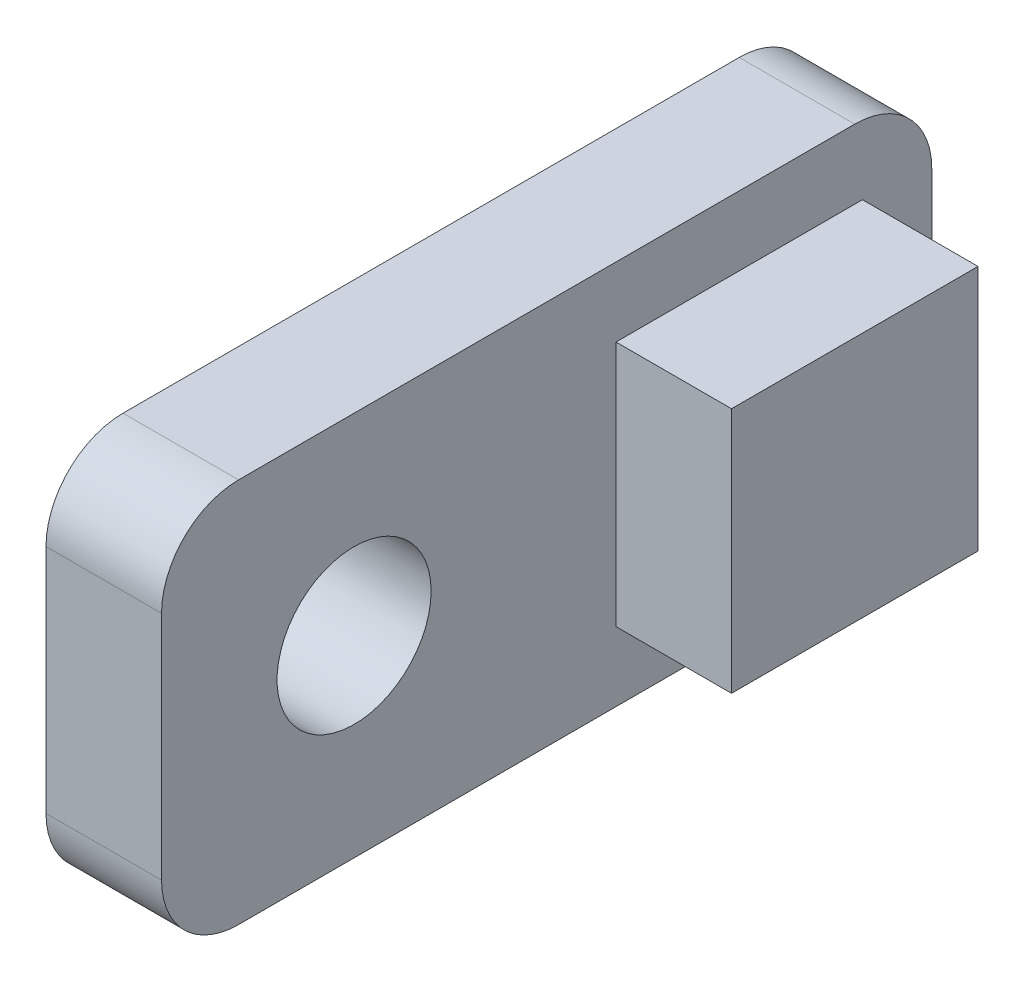
SolidWorks part; units mm, degrees
ref_plane "Front Plane" through (0, 0, 0) normal (0, 0, 1) x (1, 0, 0)
ref_plane "Top Plane" through (0, 0, 0) normal (0, 1, 0) x (1, 0, 0)
ref_plane "Right Plane" through (0, 0, 0) normal (1, 0, 0) x (0, 0, -1)
sketch "Sketch1" plane through (0, 0, 0) normal (1, 0, 0) x (0, 0, -1)
  line L0 (-5, 3.2) -> (-5, -3.2) construction
  line L1 (8, -5) -> (-8, -5)
  line L2 (10, -3) -> (10, 3)
  line L3 (8, 5) -> (-8, 5)
  line L4 (-10, -3) -> (-10, 3)
  line L5 (0, 5) -> (0, -5) construction
  line L6 (10, 0) -> (-10, 0) construction
  line L7 (1.8, -3.2) -> (8.2, -3.2)
  line L8 (1.8, -3.2) -> (1.8, 3.2)
  line L9 (1.8, 3.2) -> (8.2, 3.2)
  line L10 (8.2, -3.2) -> (8.2, 3.2)
  line L11 (5, 3.2) -> (5, -3.2) construction
  line L12 (1.8, 0) -> (8.2, 0) construction
  arc A0 (10, -3) -> (8, -5) centre (8, -3) cw
  arc A1 (-8, -5) -> (-10, -3) centre (-8, -3) cw
  arc A2 (10, 3) -> (8, 5) centre (8, 3) ccw
  arc A3 (-8, 5) -> (-10, 3) centre (-8, 3) ccw
  circle A4 centre (-5, 0) radius 2
  point P0 (0, 0)
  point P4 (5, 0)
  point P8 (0, 0)
  dimension "D6" = 2
  dimension "D7" = 4
  dimension "D1" = 20
  dimension "D2" = 10
  dimension "D3" = 6.4
  dimension "D4" = 6.4
  dimension "D5" = 5
extrude "Boss-Extrude1" add sketch "Sketch1" along normal blind 3 contours L7 L10 L9 L8 | L3 A3 L4 A1 L1 A0 L2 A2 A4 L10 L7 L8 L9 region at (0, 0, 0.9925) region at (0, 0, -5)
extrude "Boss-Extrude2" add sketch "Sketch1<3>" along normal blind 6 contours L7 L10 L9 L8 region at (0, 0, -5)
sketch "Sketch1<3>" plane through (0, 0, 0) normal (1, 0, 0) x (0, 0, -1) same geometry as "Sketch1"
